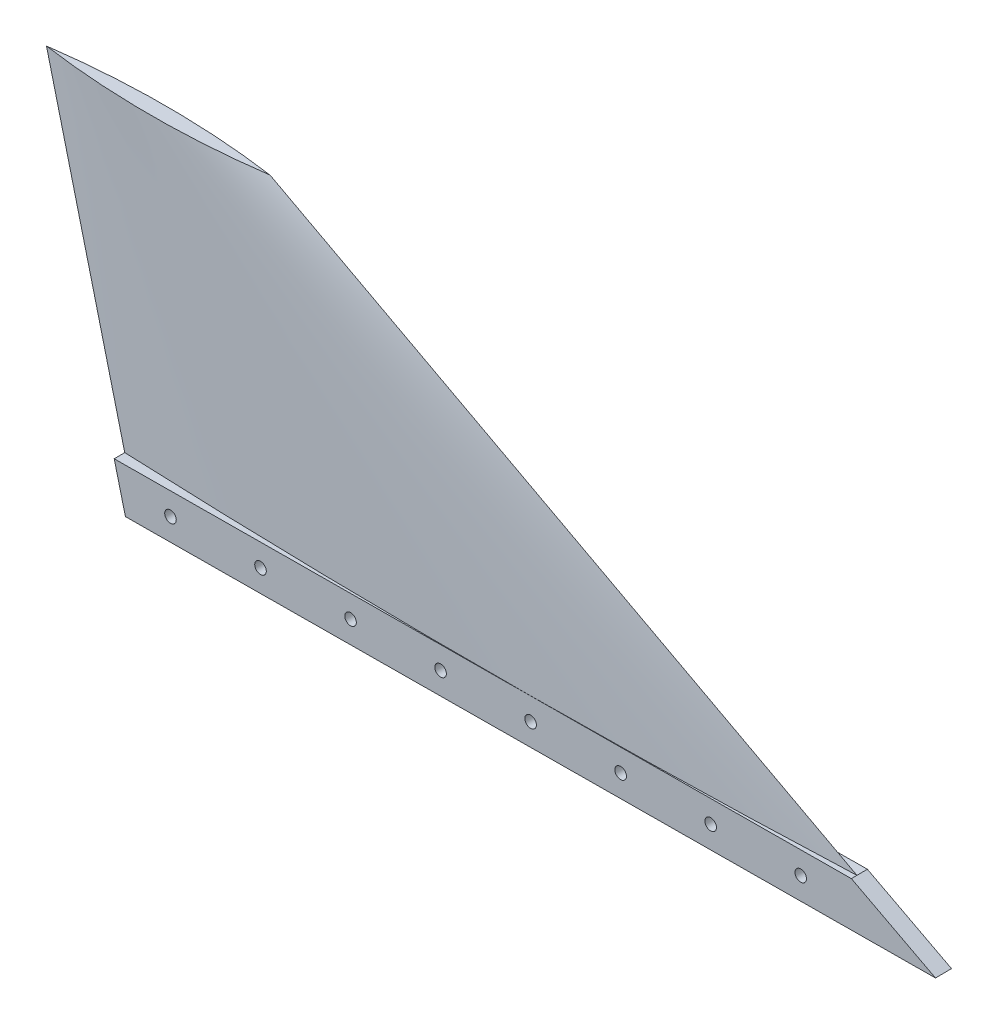
SolidWorks part; units mm, degrees
material "Aluminum Bronze"
ref_plane "Front Plane" through (0, 0, 0) normal (0, 0, 1) x (1, 0, 0)
ref_plane "Top Plane" through (0, 0, 0) normal (0, 1, 0) x (1, 0, 0)
ref_plane "Right Plane" through (0, 0, 0) normal (1, 0, 0) x (0, 0, -1)
sketch "Sketch1" plane through (0, 0, 0) normal (0, 1, 0) x (1, 0, 0)
  line L0 (0, 0) -> (457.2, 0) construction
  line L1 (228.6, 4.445) -> (228.6, 0) construction
  arc A0 (0, 0) -> (457.2, 0) centre (228.6, -5876.0632) cw
  arc A1 (0, 0) -> (457.2, 0) centre (228.6, 5876.0632) ccw
  dimension "D1" = 457.2
  dimension "D2" = 4.445
ref_plane "Plane2" through (0, 203.2, 0) normal (0, 1, 0) x (1, 0, 0)
sketch "Sketch5" plane through (0, 203.2, 0) normal (0, 1, 0) x (1, 0, 0)
  line L0 (0, 0) -> (76.2, 0) construction
  line L1 (0, 0) -> (-50.8, 0) construction
  line L2 (12.7, 4.445) -> (12.7, 0) construction
  arc A0 (-50.8, 0) -> (76.2, 0) centre (12.7, -451.3489) cw
  arc A1 (-50.8, 0) -> (76.2, 0) centre (12.7, 451.3489) ccw
  dimension "D1" = 127
  dimension "D2" = 50.8
  dimension "D3" = 4.445
loft "Loft4" add profiles "Sketch5", "Sketch1" connector at (-50.8, 203.2, 0) connector at (0, 0, 0)
ref_axis "Axis3" through (228.6, 254.2969, 0) along (0, -1, 0)
ref_axis "Axis1" through (76.2, 203.2, 0) along (-1, 0, 0)
ref_axis "Axis2" through (457.2, 0, 0) along (-1, 0, 0)
ref_plane "Plane3" through (0.0106, 0, 1.556) normal (0.0068, 0, 1) x (0, -1, 0)
ref_plane "Plane8" through (-0.0217, 0, -3.1851) normal (0.0068, 0, 1) x (0, -1, 0)
sketch "Sketch15" plane through (0, 0, 0) normal (0, -1, 0) x (1, 0, 0)
  line L0 (190.6802, 0.2581) -> (-190.659, 2.8538) construction
  line L1 (0.0418, 6.137) -> (457.2206, 3.025)
  line L2 (0.0418, 6.137) -> (-0.0206, -3.025)
  line L3 (-0.0206, -3.025) -> (457.1582, -6.137)
  line L4 (457.2206, 3.025) -> (457.1582, -6.137)
  spline S0 degree 3 poles (0, 0) (76.1424, 2.9622) (152.3712, 4.445) (304.8288, 4.445) (381.0576, 2.9622) (457.2, 0) knots 0 0 0 0 0.5 0.5 1 1 1 1 construction
  spline S1 degree 3 poles (457.2, 0) (381.0576, -2.9622) (304.8288, -4.445) (152.3712, -4.445) (76.1424, -2.9622) (0, 0) knots 0 0 0 0 0.5 0.5 1 1 1 1 construction
sketch "Sketch10" plane through (-0.0217, 0, -3.1851) normal (0.0068, 0, 1) x (0, -1, 0)
  line L0 (0, 457.1894) -> (0, 0)
  line L1 (0, 0) -> (-25.4, -6.3499)
  line L2 (0, 0) -> (-203.2, -50.7988) construction
  line L3 (-25.4, -6.3499) -> (-25.4, 409.5655)
  line L4 (-203.2, 76.1982) -> (0, 457.1894) construction
  line L5 (-25.4, 409.5655) -> (0, 457.1894)
  dimension "D1" = 25.4
extrude "Boss-Extrude1" add sketch "Sketch10" along normal blind 9.1622
ref_plane "Plane5" through (0, 0, 0) normal (-1, 0, 0.0068) x (-0.0068, 0, -1)
sketch "Sketch12" plane through (0, 0, 0) normal (-1, 0, 0.0068) x (0.0068, 0, 1)
  line L2 (12.327, 0) -> (12.327, 25.4)
  line L4 (-9.5351, 0) -> (-9.5351, 25.4)
  line L5 (12.327, 25.4) -> (5.977, 25.4)
  line L6 (12.327, 25.4) -> (12.327, 0)
  line L7 (12.327, 0) -> (5.977, 0)
  line L8 (5.977, 25.4) -> (5.977, 0)
  line L9 (-9.5351, 25.4) -> (-3.1851, 25.4)
  line L10 (-9.5351, 25.4) -> (-9.5351, 0)
  line L11 (-9.5351, 0) -> (-3.1851, 0)
  line L12 (-3.1851, 25.4) -> (-3.1851, 0)
  line L14 (5.977, 0) -> (-3.1851, 0) construction
  dimension "D1" = 6.35
extrude "Cut-Extrude1" cut sketch "Sketch12" against normal through all both and the other way through all contours L5 L8 L7 L2 | L12 L9 L4 L11 region at (0.0623, 12.7, 9.1518) region at (-0.0433, 12.7, -6.36)
ref_plane "Plane4" through (0.097, 0, 14.2557) normal (0.0068, 0, 1) x (0, -1, 0)
hole_wizard "1/4 Clearance Hole1" positions "Sketch8" profile "Sketch9" hole size "1/4" standard "ANSI Inch" end condition through all
sketch "Sketch8" plane through (0.097, 0, 14.2557) normal (0.0068, 0, 1) x (0, -1, 0)
  point P0 (-12.7, 25.4)
  dimension "D1" = 12.7
  dimension "D2" = 25.4
sketch "Sketch9" plane through (25.4964, 12.7, 14.0828) normal (0, 1, 0) x (1, 0, -0.0068)
  line L0 (0, 0) -> (0, 22.0318)
  line L1 (0, 22.0318) -> (3.2639, 22.0318)
  line L2 (3.2639, 22.0318) -> (3.2639, 0)
  line L5 (3.2639, 0) -> (0, 0)
  line L11 (0, -6.35) -> (0, 107.95) construction
  dimension "Thru Hole Dia." = 6.5278
  dimension "Thru Hole Depth" = 22.0318
pattern_linear "LPattern1" count 8 spacing 50.8 along (1, 0, 0) of "1/4 Clearance Hole1"
sketch "Sketch13" [suppressed] plane through (0, 0, 0) normal (0, -1, 0) x (1, 0, 0)
  line L0 (3.8884, 5.2873) -> (445.7919, 2.2793) construction
  line L1 (0.0362, 5.3135) -> (457.215, 2.2016) construction
  line L2 (-3.917, -2.5424) -> (450.1427, -5.6332) construction
  line L3 (-0.0175, -2.569) -> (457.1613, -5.6809) construction
  spline S0 degree 3 poles (-6.35, 0) (62.9148, 2.5382) (132.2636, 3.81) (214.4874, 3.81) (227.3622, 3.7662) (240.2365, 3.6785) knots 0.407173 0.407173 0.407173 0.407173 0.907173 0.907173 1 1 1 1 construction
  spline S1 degree 3 poles (227.5601, -3.7507) (218.911, -3.7902) (175.8551, -3.8887) (132.7993, -3.497) (98.403, -2.8715) knots 0.251931 0.251931 0.251931 0.251931 0.314292 0.562361 0.562361 0.562361 0.562361 construction
sketch "Sketch14" plane through (0.0407, 0, 5.9769) normal (0.0068, 0, 1) x (1, 0, -0.0068)
  line L0 (0, 0) -> (457.1894, 0) construction
  line L1 (-0.019, 0.0762) -> (457.1894, 0.0762)
  line L2 (-0.019, 0.0762) -> (-0.019, -25.3238)
  line L3 (-0.019, -25.3238) -> (457.1894, -25.3238)
  line L4 (457.1894, 0.0762) -> (457.1894, -25.3238)
  line L5 (-6.3499, 25.4) -> (0, 0) construction
  dimension "D1" = 0.0762
  dimension "D2" = 25.4
extrude "Cut-Extrude2" cut sketch "Sketch14" against normal through all
equation "\"D1@Plane8\"=0.18666013"
equation "\"D1@Boss-Extrude1\"=0.36071577"
